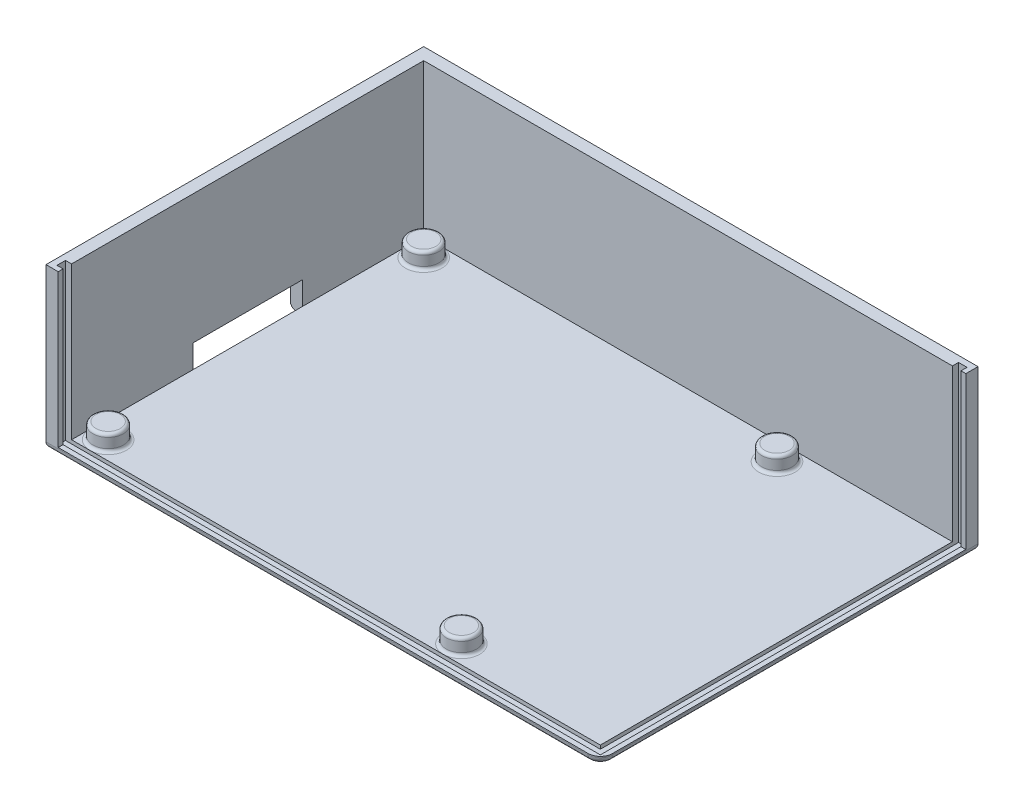
SolidWorks part; units mm, degrees
other "Markup1"
sketch "Sketch1" plane through (89, 19.2, 0) normal (0.8232, 0.4717, 0.3158) x (0.2894, 0.13, -0.9484)
sketch "Skica14" plane through (89, 26.2, 0) normal (0.8232, 0.4717, 0.3158) x (0.2894, 0.13, -0.9484)
sketch "Sketch5" plane through (89, 26.2, 0) normal (0.8232, 0.4717, 0.3158) x (0.2894, 0.13, -0.9484)
sketch "Sketch14" plane through (89, 26.2, 0) normal (0.8232, 0.4717, 0.3158) x (0.2894, 0.13, -0.9484)
sketch "Skica16" plane through (89, 26.2, 0) normal (0.8232, 0.4717, 0.3158) x (0.2894, 0.13, -0.9484)
sketch "Sketch16" plane through (89, 26.2, 0) normal (0.8232, 0.4717, 0.3158) x (0.2894, 0.13, -0.9484)
sketch "Sketch18" plane through (91, 26.2, 0) normal (0.8232, 0.4717, 0.3158) x (0.2894, 0.13, -0.9484)
sketch "Sketch19" plane through (91, 26.2, 0) normal (0.8232, 0.4717, 0.3158) x (0.2894, 0.13, -0.9484)
ref_plane "Přední rovina" through (0, 0, 0) normal (0, 0, 1) x (1, 0, 0)
ref_plane "Horní rovina" through (0, 0, 0) normal (0, 1, 0) x (1, 0, 0)
ref_plane "Pravá rovina" through (0, 0, 0) normal (1, 0, 0) x (0, 0, -1)
sketch "Skica1" plane through (0, 0, 0) normal (0, 1, 0) x (1, 0, 0)
  line L5 (0, 0) -> (91, 0)
  line L6 (0, 0) -> (0, 62)
  line L7 (0, 62) -> (91, 62)
  line L8 (91, 0) -> (91, 62)
  dimension "D3" = 62
  dimension "D4" = 91
extrude "Přidat vysunutím5" add sketch "Skica1" along normal blind 1.2 contours L7 L8 L5 L6
sketch "Skica5" plane through (0, 1.2, 0) normal (0, 1, 0) x (1, 0, 0)
  line L1 (0, 0) -> (91, 0)
  line L2 (0, 0) -> (0, 62)
  line L3 (0, 62) -> (91, 62)
  line L4 (91, 0) -> (91, 62)
  line L5 (2, 0) -> (91, 0)
  line L6 (2, 0) -> (2, 60)
  line L7 (2, 60) -> (91, 60)
  line L8 (91, 0) -> (91, 60)
  line M9 (0, 62) -> (0, 0)
  line M10 (0, 0) -> (91, 0)
  line M12 (91, 62) -> (0, 62)
  dimension "D1" = 60
  dimension "D2" = 89
  dimension "D3" = 2
  dimension "D4" = 2
extrude "Přidat vysunutím8" add sketch "Skica5" along normal blind 25 contours L6 L7 L4 M12 M9 M10 region at (1.1011, 1.2, -31)
sketch "Skica13" plane through (0, 1.2, 0) normal (0, 1, 0) x (1, 0, 0)
  line L0 (2, 0) -> (91, 0) construction
  line L1 (1, 0.8) -> (88.8, 0.8)
  line L2 (1, 0.8) -> (1, 2.2)
  line L3 (1, 2.2) -> (88.8, 2.2)
  line L4 (88.8, 0.8) -> (88.8, 2.2)
  line L5 (90.2, 61) -> (88.8, 61)
  line L6 (90.2, 61) -> (90.2, 0.8)
  line L7 (90.2, 0.8) -> (88.8, 0.8)
  line L8 (88.8, 61) -> (88.8, 0.8)
  line L9 (0, 62) -> (0, 0) construction
  line L10 (91, 0) -> (91, 60) construction
  line L11 (91, 62) -> (0, 62) construction
  line M1 (2, 60) -> (2, 0)
  dimension "D1" = 1.4
  dimension "D2" = 0.8
  dimension "D3" = 0.8
  dimension "D4" = 1
  dimension "D5" = 1
  dimension "D6" = 1.4
extrude "Odebrat vysunutím2" cut sketch "Skica13" along normal up to next from offset 0.6 contours L1 L4 L3 M1 | L7 L6 L5 L8 | L2 L1 L4 L3 region at (45.4, 1.2, -1.5) offset against normal yes
sketch "Sketch2" plane through (2, 0, 0) normal (1, 0, 0) x (0, 0, -1)
  line L0 (31.1, 1.2) -> (31.1, 26.2) construction
  line L1 (0, 0) -> (62, 0) construction
  line L2 (22.1, 0) -> (40.1, 0)
  line L3 (22.1, 0) -> (22.1, 5)
  line L4 (2.2, 1.2) -> (60, 1.2) construction
  line L5 (2.2, 26.2) -> (60, 26.2) construction
  line L6 (22.1, 5) -> (40.1, 5)
  line L19 (40.1, 0) -> (40.1, 5)
  point P12 (31.1, 5)
  dimension "D1" = 18
  dimension "D2" = 5
other "AlignGroup1"
other "AlignGroup2"
extrude "Cut-Extrude2" cut sketch "Sketch2" against normal up to next
sketch "Sketch4" plane through (0, 1.2, 0) normal (0, 1, 0) x (1, 0, 0)
  line L1 (2, 2.2) -> (88.8, 2.2) construction
  line L2 (2, 31.1) -> (88.8, 31.1) construction
  line L3 (2, 22.1) -> (2, 40.1) construction
  line L4 (1, 2.2) -> (88.8, 2.2) construction
  line L5 (2, 2.2) -> (2, 22.1) construction
  line L7 (88.8, 60) -> (88.8, 2.2) construction
  circle A0 centre (63, 5.2) radius 2.5
  circle A1 centre (63, 57) radius 2.5
  circle A2 centre (5, 5.2) radius 2.5
  circle A3 centre (5, 57) radius 2.5
  dimension "D1" = 5
  dimension "D4" = 5
  dimension "D5" = 3
  dimension "D2" = 58
  dimension "D3" = 3
  dimension "D6" = 3
extrude "Odebrat vysunutím6" cut sketch "Sketch4" against normal blind 0.4
sketch "Sketch17" plane through (0, 0.8, 0) normal (0, 1, 0) x (1, 0, 0)
  line L0 (2, 31.1) -> (88.8, 31.1) construction
  line L1 (2, 2.2) -> (2, 60) construction
  line L2 (88.8, 2.2) -> (88.8, 60) construction
  line L3 (5, 5.2) -> (63, 5.2) construction
  line L4 (34, 5.2) -> (34, 2.2) construction
  line L5 (1, 2.2) -> (88.8, 2.2) construction
  circle A0 centre (5, 5.2) radius 2.5
  circle A1 centre (5, 5.2) radius 2.5 construction
  circle A2 centre (5, 57) radius 2.5
  circle A3 centre (63, 57) radius 2.5
  circle A4 centre (63, 5.2) radius 2.5
extrude "Boss-Extrude3" add sketch "Sketch17" along normal blind 3
fillet "Fillet24" radius 0.5 4 edges at (5, 1.2, -2.7) (63, 1.2, -59.5) (5, 1.2, -59.5) (63, 1.2, -2.7)
fillet "Fillet25" radius 0.5 4 edges at (63, 3.8, -7.7) (63, 3.8, -54.5) (5, 3.8, -59.5) (5, 3.8, -2.7)
fillet "Fillet2" radius 1 5 edges at (0, 0, -11.05) (0, 0, -51.05) (45.5, 0, -62) (91, 0, -31) (45.5, 0, 0)
fillet "Fillet5" radius 2 2 edges at (90.7071, 0.2929, -0.2929) (91, 1.1, 0)
